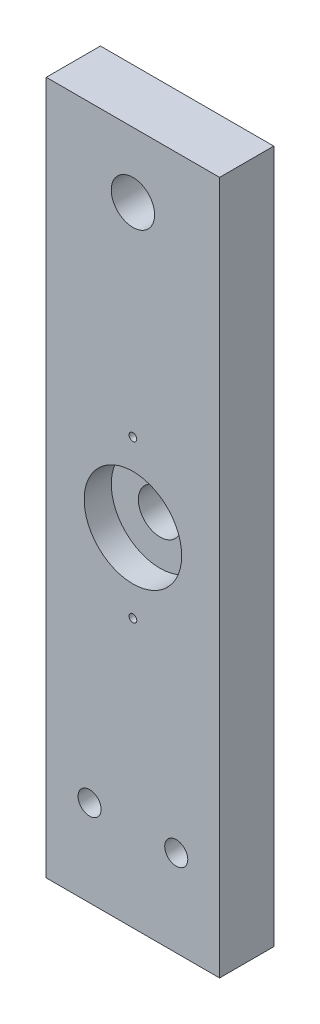
SolidWorks part; units mm, degrees
ref_plane "Front Plane" through (0, 0, 0) normal (0, 0, 1) x (1, 0, 0)
ref_plane "Top Plane" through (0, 0, 0) normal (0, 1, 0) x (1, 0, 0)
ref_plane "Right Plane" through (0, 0, 0) normal (1, 0, 0) x (0, 0, -1)
sketch "Sketch1" plane through (0, 0, 0) normal (0, 0, 1) x (1, 0, 0)
  line L0 (25.4, 177.8) -> (-25.4, 177.8) construction
  line L1 (-25.4, -25.4) -> (25.4, -25.4)
  line L2 (-25.4, -25.4) -> (-25.4, 177.8)
  line L3 (-25.4, 177.8) -> (25.4, 177.8)
  line L4 (25.4, -25.4) -> (25.4, 177.8)
  line L5 (25.4, 25.4) -> (25.4, -25.4) construction
extrude "Boss-Extrude1" add sketch "Sketch1" along normal blind 15.875 contours L4 L3 L2 L1
sketch "Sketch2" plane through (0, 0, 15.875) normal (0, 0, 1) x (1, 0, 0)
  circle A0 centre (-12.7, 0) radius 3.3782 construction
  circle A1 centre (12.7, 0) radius 3.3782 construction
  circle A2 centre (-12.7, 0) radius 3.3782
  circle A3 centre (12.7, 0) radius 3.3782
hole_wizard "1/4 Clearance Hole1" positions "Sketch3" profile "Sketch4" hole size "1/4" standard "ANSI Inch" end condition through all
sketch "Sketch3" plane through (0, 0, 15.875) normal (0, 0, 1) x (1, 0, 0)
  point P0 (12.7, 0)
  point P3 (-12.7, 0)
sketch "Sketch4" plane through (12.7, 0, 15.875) normal (1, 0, 0) x (0, -1, 0)
  line L0 (0, 0) -> (0, 15.875)
  line L1 (0, 15.875) -> (3.3782, 15.875)
  line L2 (3.3782, 15.875) -> (3.3782, 0)
  line L5 (3.3782, 0) -> (0, 0)
  line L11 (0, -6.35) -> (0, 107.95) construction
  dimension "Thru Hole Dia." = 6.7564
  dimension "Thru Hole Depth" = 15.875
sketch "Sketch5" plane through (0, 0, 0) normal (0, 0, -1) x (-1, 0, 0)
  circle A0 centre (0, 158.75) radius 6.35 construction
  circle A1 centre (0, 158.75) radius 6.35
  circle A2 centre (0, 76.2) radius 6.35 construction
  circle A3 centre (0, 76.2) radius 6.35
extrude "Cut-Extrude1" cut sketch "Sketch5" against normal through all
sketch "Sketch6" plane through (0, 0, 15.875) normal (0, 0, 1) x (1, 0, 0)
  circle A0 centre (0, 76.2) radius 14.2875 construction
  circle A1 centre (0, 76.2) radius 14.2875
extrude "Cut-Extrude2" cut sketch "Sketch6" against normal blind 7.9375 contours A1
sketch "Sketch7" plane through (0, 0, 15.875) normal (0, 0, 1) x (1, 0, 0)
  line L0 (0, 53.213) -> (0, 99.187)
  circle A0 centre (0, 76.2) radius 14.2875 construction
  point P5 (0, 76.2)
  dimension "D1" = 45.974
hole_wizard "#4-40 Tapped Hole1" positions "Sketch8" profile "Sketch9" tap size "#4-40" standard "ANSI Inch"
sketch "Sketch8" plane through (0, 0, 15.875) normal (0, 0, 1) x (1, 0, 0)
  point P0 (0, 99.187)
  point P3 (0, 53.213)
sketch "Sketch9" plane through (0, 99.187, 15.875) normal (1, 0, 0) x (0, -1, 0)
  line L0 (0, 0) -> (0, 8.2992)
  line L1 (0, 8.2992) -> (1.1303, 7.62)
  line L2 (1.1303, 7.62) -> (1.1303, 0)
  line L5 (1.1303, 0) -> (0, 0)
  line L10 (0, 8.2992) -> (-1.1303, 7.62) construction
  line L11 (0, -6.35) -> (0, 107.95) construction
  dimension "Tap Drill Dia." = 2.2606
  dimension "Tap Drill Depth" = 7.62
  dimension "Drill Angle" = 118
cosmetic thread "Hole Thread1" parameters "D1"=5.588, "D2"=2.8448
cosmetic thread "Hole Thread2" parameters "D1"=5.588, "D2"=2.8448
hole_wizard "1/4-20 Tapped Hole1" positions "Sketch10" profile "Sketch11" tap size "1/4-20" standard "ANSI Inch"
sketch "Sketch10" plane through (-25.4, 0, 0) normal (-1, 0, 0) x (0, 0, 1)
  line L0 (15.875, 177.8) -> (0, 177.8) construction
  point P0 (7.9375, 139.7)
  point P2 (7.9375, 107.95)
  point P8 (7.9375, 177.8)
  dimension "D1" = 38.1
  dimension "D2" = 31.75
sketch "Sketch11" plane through (-25.4, 139.7, 7.9375) normal (0, 1, 0) x (0, 0, 1)
  line L0 (0, 0) -> (0, 18.0438)
  line L1 (0, 18.0438) -> (2.5527, 16.51)
  line L2 (2.5527, 16.51) -> (2.5527, 0)
  line L5 (2.5527, 0) -> (0, 0)
  line L10 (0, 18.0438) -> (-2.5527, 16.51) construction
  line L11 (0, -6.35) -> (0, 107.95) construction
  dimension "Tap Drill Dia." = 5.1054
  dimension "Tap Drill Depth" = 16.51
  dimension "Drill Angle" = 118
cosmetic thread "Hole Thread3" parameters "D1"=12.7, "D2"=6.35
cosmetic thread "Hole Thread4" parameters "D1"=12.7, "D2"=6.35
equation "\"UprightThickness\"=0.625"
equation "\"D1@Boss-Extrude1\"=\"UprightThickness\""
